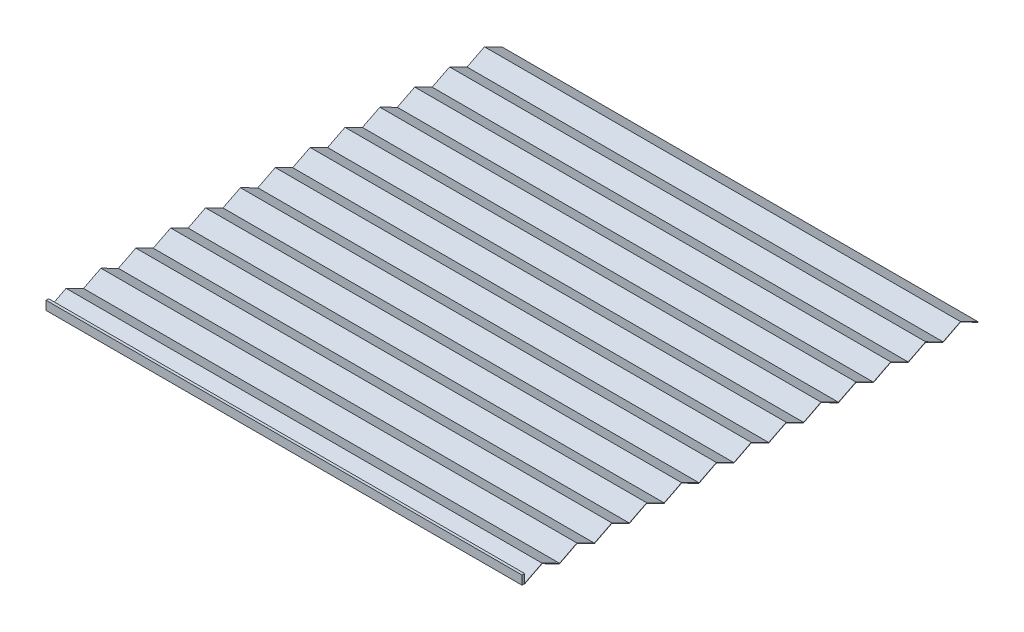
SolidWorks part; units mm, degrees
ref_plane "Front Plane" through (0, 0, 0) normal (0, 0, 1) x (1, 0, 0)
ref_plane "Top Plane" through (0, 0, 0) normal (0, 1, 0) x (1, 0, 0)
ref_plane "Right Plane" through (0, 0, 0) normal (1, 0, 0) x (0, 0, -1)
sketch "Sketch2" plane through (0, 0, 0) normal (0, 0, 1) x (1, 0, 0)
  line L1 (-270, 10) -> (270, 10)
  line L2 (-270, 10) -> (-270, 0)
  line L3 (-270, 0) -> (270, 0)
  line L4 (270, 10) -> (270, 0)
  point P4 (0, 0)
  dimension "D1" = 10
  dimension "D2" = 540
extrude "Boss-Extrude1" add sketch "Sketch2" along normal blind 3
sketch "Sketch3" plane through (270, 0, 0) normal (1, 0, 0) x (0, 0, -1)
  line L0 (0, 10) -> (514.1932, 10) construction
  line L1 (0, 0) -> (514.1932, 0) construction
  line L2 (514.1932, 10) -> (514.1932, 0) construction
  line L3 (0, 0) -> (19.7767, 10)
  line L4 (19.7767, 10) -> (39.5533, 0)
  line L5 (39.5533, 0) -> (59.33, 10)
  line L6 (59.33, 10) -> (79.1067, 0)
  line L7 (79.1067, 0) -> (98.8833, 10)
  line L8 (98.8833, 10) -> (118.66, 0)
  line L9 (118.66, 0) -> (138.4366, 10)
  line L10 (138.4366, 10) -> (158.2133, 0)
  line L11 (158.2133, 0) -> (177.99, 10)
  line L12 (177.99, 10) -> (197.7666, 0)
  line L13 (197.7666, 0) -> (217.5433, 10)
  line L14 (217.5433, 10) -> (237.32, 0)
  line L15 (237.32, 0) -> (257.0966, 10)
  line L16 (257.0966, 10) -> (276.8733, 0)
  line L17 (276.8733, 0) -> (296.6499, 10)
  line L18 (296.6499, 10) -> (316.4266, 0)
  line L20 (316.4266, 0) -> (336.2033, 10)
  line L21 (336.2033, 10) -> (355.9799, 0)
  line L22 (355.9799, 0) -> (375.7566, 10)
  line L23 (375.7566, 10) -> (395.5333, 0)
  line L24 (395.5333, 0) -> (415.3099, 10)
  line L25 (415.3099, 10) -> (435.0866, 0)
  line L26 (435.0866, 0) -> (454.8632, 10)
  line L27 (454.8632, 10) -> (474.6399, 0)
  line L28 (474.6399, 0) -> (494.4166, 10)
  line L29 (494.4166, 10) -> (514.1932, 0)
  line L30 (514.1932, 10) -> (514.1932, 0) construction
extrude "Extrude-Thin1" add sketch "Sketch3" against normal through all thin thin type mid plane wall 0.5
